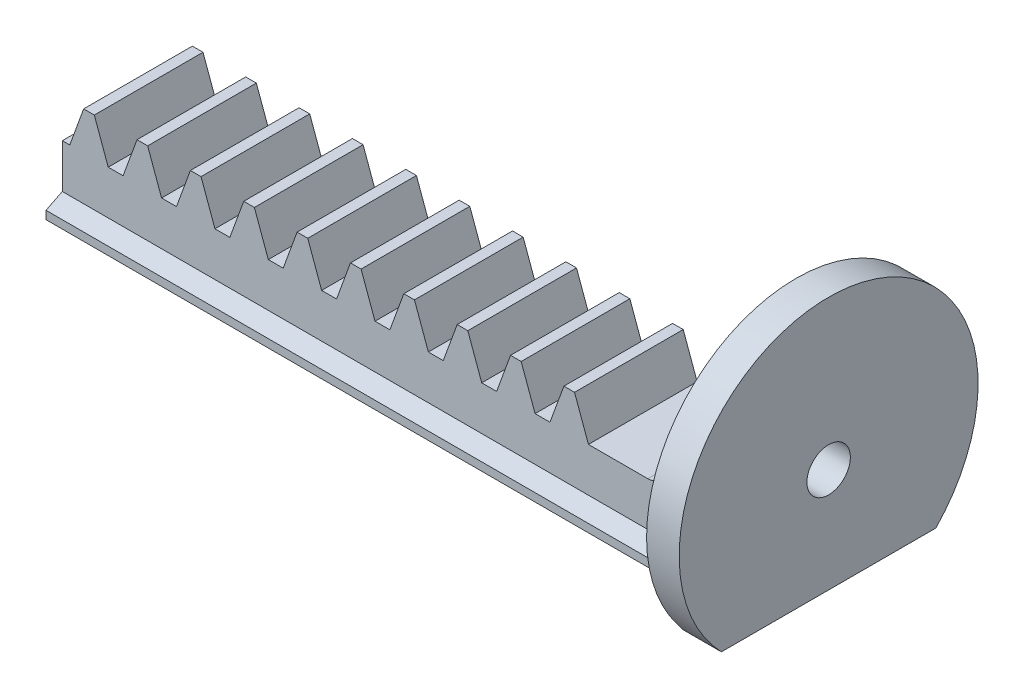
SolidWorks part; units mm, degrees
extrude "Blank" add sketch "BlankSke" against normal blind 6
sketch "BlankSke" plane through (0, 0, 0) normal (0, 0, 1) x (1, 0, 0)
  line L1 (0, 0) -> (40, 0)
  line L2 (0, 0) -> (0, 7.25)
  line L3 (0, 7.25) -> (40, 7.25)
  line L4 (40, 0) -> (40, 7.25)
  dimension "Length" = 40
  dimension "Blank_height" = 7.25
material "1060 合金"
ref_plane "Plane1" through (0, 0, 0) normal (0, 0, 1) x (1, 0, 0)
ref_plane "Plane2" through (0, 0, 0) normal (0, 1, 0) x (1, 0, 0)
ref_plane "Plane3" through (0, 0, 0) normal (1, 0, 0) x (0, 0, -1)
other "Configuration Table"
sketch "HoldingSke" plane through (0, 0, 0) normal (0, 1, 0) x (1, 0, 0)
  line L0 (0, 0) -> (0.1113, 0.7922)
  line L1 (-15, 0) -> (100, 0) construction
  line L2 (0, 0) -> (-2.1039, 2.3779)
  line L3 (0, 0) -> (-11.863, 4.5341)
  line L4 (0, 0) -> (8.4473, 1.7955)
  line L5 (0, 0) -> (-23.7986, -8.8762)
  line L6 (0, 0) -> (-10.5278, -7.1032)
  line L9 (-71.009, 38.7566) -> (-33.4213, 52.4374)
  line L10 (-76.2, 3.6279) -> (-70.2, 3.6279)
  line L11 (0, 0) -> (-6, 0)
  line L12 (-76.2, 101.6) -> (-76.155, 101.6)
  line L13 (24.9733, 27.94) -> (52.9518, 28.4284)
  line L14 (24.9733, 27.94) -> (24.9743, 27.94)
  line L15 (24.9733, 27.94) -> (100.4006, 29.5858)
  circle A0 centre (0, 0) radius 19.05
  circle A1 centre (0, 0) radius 3
  circle A2 centre (0, 0) radius 12.7
  dimension "MPH" = 6
  dimension "Diameter" = 38.1
  dimension "Num_teeth" = 12
  dimension "Pitch" = 0.8
  dimension "Show_teeth" = 998
  dimension "Thickness" = 12.7
  dimension "Ap" = 20
  dimension "Pitch_height" = 6
  dimension "Width" = 6
  dimension "Backlash" = 0.045
  dimension "Addendum_fac" = 1
  dimension "Dedendum_fac" = 1.25
  dimension "Clearance_fac" = 0.25
  dimension "Dedendum_add" = 0.001
  dimension "Length" = 40
  dimension "Module" = 1.25
sketch "TooCutSkeIll" plane through (0, 0, 0) normal (0, 0, 1) x (1, 0, 0)
  line L0 (-1.5597, 7.2171) -> (-0.6231, 4.6438)
  line L1 (-0.3285, 4.4375) -> (0.3285, 4.4375)
  line L2 (0.6231, 4.6438) -> (1.5597, 7.2171)
  line L3 (40, 7.25) -> (0, 7.25) construction
  line L4 (0, 0) -> (0, 64.897) construction
  line L5 (-13.208, 6) -> (12.954, 6) construction
  line L6 (0, 0) -> (40, 0) construction
  line L7 (1.1167, 6) -> (1.1167, 48.7463) construction
  line L8 (-1.1167, 6) -> (-1.1167, 48.7463) construction
  line L9 (1.6067, 7.25) -> (1.6067, 7.2754)
  line L10 (-1.6067, 7.25) -> (-1.6067, 7.2754)
  line L11 (-1.6067, 7.2754) -> (1.6067, 7.2754)
  arc A0 (0.3285, 4.4375) -> (0.6231, 4.6438) centre (0.3285, 4.751) ccw
  arc A1 (-0.6231, 4.6438) -> (-0.3285, 4.4375) centre (-0.3285, 4.751) ccw
  arc A2 (1.6067, 7.25) -> (1.5597, 7.2171) centre (1.6067, 7.2) ccw
  arc A3 (-1.5597, 7.2171) -> (-1.6067, 7.25) centre (-1.6067, 7.2) ccw
  dimension "Pitch_height" = 6
  dimension "Addendum_plus" = 1.2754
  dimension "Pressure_angle" = 20
  dimension "Gap_width" = 2.2335
  dimension "Dedendum" = 1.5625
extrude "ToothCutIll" [suppressed] cut sketch "TooCutSkeIll" against normal through all
sketch "TooCutSkeSim" plane through (0, 0, 0) normal (0, 0, 1) x (1, 0, 0)
  line L0 (0.548, 4.4375) -> (-0.548, 4.4375)
  line L1 (1.581, 7.2754) -> (0.548, 4.4375)
  line L2 (0, 17.4625) -> (0, 53.467) construction
  line L3 (1.581, 7.2754) -> (-1.581, 7.2754)
  line L6 (-1.581, 7.2754) -> (-0.548, 4.4375)
  line L9 (-1.1167, 6) -> (1.1167, 6) construction
  line L10 (0, 0) -> (40, 0) construction
  line L11 (1.1167, 6) -> (1.1167, 53.467) construction
  line L12 (-1.1167, 6) -> (-1.1167, 53.467) construction
  dimension "Pitch_height" = 6
  dimension "Addendum_plus" = 1.2754
  dimension "Pressure_angle" = 20
  dimension "Gap_width" = 2.2335
  dimension "Dedendum" = 1.5625
extrude "ToothCutSim" cut sketch "TooCutSkeSim" against normal through all
pattern_linear "TeethCuts" count 12 spacing 3.927 along (1, 0, 0) of "ToothCutIll", "ToothCutSim"
sketch "草图1" plane through (0, 0, 0) normal (0, 0, 1) x (1, 0, 0)
  line L0 (39.818, 4.4375) -> (41.3726, 4.4375)
  line L1 (41.3726, 4.4375) -> (41.3726, 5.3432)
  line L2 (41.3726, 5.3432) -> (39.818, 5.3432)
  line L3 (39.818, 5.3432) -> (39.818, 4.4375)
extrude "切除-拉伸1" cut sketch "草图1" against normal blind 10
sketch "草图2" plane through (0, 0, 0) normal (0, -1, 0) x (1, 0, 0)
  line L0 (40, 0) -> (50, 0)
  line L2 (50, 0) -> (50, -6)
  line L3 (50, -6) -> (40, -6)
  line L4 (40, -6) -> (40, 0)
  dimension "D1" = 10
extrude "凸台-拉伸1" add sketch "草图2" against normal up to surface (4.4375 mm away)
sketch "草图3" plane through (50, 0, 0) normal (1, 0, 0) x (0, 0, -1)
  line L0 (0, 4.4375) -> (0, 10.8887)
  line L1 (0, 10.8887) -> (6, 10.8887)
  line L2 (6, 10.8887) -> (6, 4.4375)
  line L3 (6, 4.4375) -> (6, 0) construction
  line L4 (0, 4.4375) -> (0, 0) construction
  line L5 (6, 0) -> (0, 0) construction
  line L6 (0, 4.4375) -> (0, 0)
  line L7 (6, 4.4375) -> (6, 0)
  line L8 (6, 0) -> (0, 0)
extrude "凸台-拉伸2" add sketch "草图3" along normal blind 2.4
sketch "草图4" plane through (50, 0, 0) normal (-1, 0, 0) x (0, 0, 1)
  line L0 (-6, 10.8887) -> (0, 4.4375) construction
  line L1 (0, 10.8887) -> (-6, 4.4375) construction
  line L2 (-6, 10.8887) -> (0, 10.8887) construction
  point P10 (-3, 7.6631)
  point P14 (-3, 7.6631)
hole_wizard "Ø3.0mm 暗销孔1" positions "草图4" profile "草图5" hole size "Ø3.0" standard "ISO" end condition through all
sketch "草图5" plane through (50, 7.6631, -3) normal (0, 1, 0) x (0, 0, 1)
  line L0 (0, 0) -> (0, 2.4)
  line L1 (0, 2.4) -> (1.6, 2.4)
  line L2 (1.6, 2.4) -> (1.6, 0)
  line L5 (1.6, 0) -> (0, 0)
  line L11 (0, -6.35) -> (0, 107.95) construction
  dimension "通孔孔直径" = 3.2
  dimension "通孔孔深度" = 2.4
sketch "草图6" plane through (0, 0, -6) normal (0, 0, -1) x (-1, 0, 0)
  line L0 (-38.7219, 4.4375) -> (-50, 4.4375) construction
  line L1 (0, 0) -> (-52.4, 0) construction
  line L2 (-52.4, 0) -> (-52.4, 10.8887) construction
  line L3 (-52.4, 10.8887) -> (-50, 10.8887) construction
  line L5 (-38.7219, 4.4375) -> (-43.5, 4.4375)
  line L6 (-38.7219, 0) -> (-52.4, 0)
  line L7 (-52.4, 0) -> (-52.4, 10.8887)
  line L8 (-52.4, 10.8887) -> (-50, 10.8887)
  line L10 (-38.7219, 4.4375) -> (-38.7219, 0)
  line L11 (-50, 10.8887) -> (-43.5, 4.4375)
  dimension "D1" = 6.5
extrude "凸台-拉伸3" add sketch "草图6" along normal blind 1
ref_plane "基准面1" through (0, 0, -3) normal (0, 0, -1) x (-1, 0, 0)
mirror "镜向1" about plane through (0, 0, -3) normal (0, 0, -1) of "凸台-拉伸3"
fillet "圆角1" radius 1 3 edges at (50, 4.4375, -3) (43.5, 4.4375, 0.5) (43.5, 4.4375, -6.5)
sketch "草图9" plane through (0, 0, -7) normal (0, 0, -1) x (-1, 0, 0)
  line L43 (-37.6982, 7.25) -> (-38.7219, 4.4375)
  line L44 (-38.7219, 4.4375) -> (-38.7219, 0)
  line L45 (-38.7219, 0) -> (0, 0)
  line L46 (0, 0) -> (0, 4.4375)
  line L47 (0, 4.4375) -> (-0.548, 4.4375)
  line L48 (-0.548, 4.4375) -> (-1.5717, 7.25)
  line L49 (-1.5717, 7.25) -> (-2.3553, 7.25)
  line L50 (-2.3553, 7.25) -> (-3.3789, 4.4375)
  line L51 (-3.3789, 4.4375) -> (-4.475, 4.4375)
  line L52 (-4.475, 4.4375) -> (-5.4987, 7.25)
  line L53 (-5.4987, 7.25) -> (-6.2823, 7.25)
  line L54 (-6.2823, 7.25) -> (-7.3059, 4.4375)
  line L55 (-7.3059, 4.4375) -> (-8.402, 4.4375)
  line L56 (-8.402, 4.4375) -> (-9.4257, 7.25)
  line L57 (-9.4257, 7.25) -> (-10.2093, 7.25)
  line L58 (-10.2093, 7.25) -> (-11.2329, 4.4375)
  line L59 (-11.2329, 4.4375) -> (-12.329, 4.4375)
  line L60 (-12.329, 4.4375) -> (-13.3527, 7.25)
  line L61 (-13.3527, 7.25) -> (-14.1363, 7.25)
  line L62 (-14.1363, 7.25) -> (-15.1599, 4.4375)
  line L63 (-15.1599, 4.4375) -> (-16.256, 4.4375)
  line L64 (-16.256, 4.4375) -> (-17.2797, 7.25)
  line L65 (-17.2797, 7.25) -> (-18.0632, 7.25)
  line L66 (-18.0632, 7.25) -> (-19.0869, 4.4375)
  line L67 (-19.0869, 4.4375) -> (-20.183, 4.4375)
  line L68 (-20.183, 4.4375) -> (-21.2067, 7.25)
  line L69 (-21.2067, 7.25) -> (-21.9902, 7.25)
  line L70 (-21.9902, 7.25) -> (-23.0139, 4.4375)
  line L71 (-23.0139, 4.4375) -> (-24.11, 4.4375)
  line L72 (-24.11, 4.4375) -> (-25.1337, 7.25)
  line L73 (-25.1337, 7.25) -> (-25.9172, 7.25)
  line L74 (-25.9172, 7.25) -> (-26.9409, 4.4375)
  line L75 (-26.9409, 4.4375) -> (-28.037, 4.4375)
  line L76 (-28.037, 4.4375) -> (-29.0606, 7.25)
  line L77 (-29.0606, 7.25) -> (-29.8442, 7.25)
  line L78 (-29.8442, 7.25) -> (-30.8679, 4.4375)
  line L79 (-30.8679, 4.4375) -> (-31.964, 4.4375)
  line L80 (-31.964, 4.4375) -> (-32.9876, 7.25)
  line L81 (-32.9876, 7.25) -> (-33.7712, 7.25)
  line L82 (-33.7712, 7.25) -> (-34.7949, 4.4375)
  line L83 (-34.7949, 4.4375) -> (-35.891, 4.4375)
  line L84 (-35.891, 4.4375) -> (-36.9146, 7.25)
  line L85 (-36.9146, 7.25) -> (-37.6982, 7.25)
  line L86 (-37.6982, 7.25) -> (-38.7219, 4.4375)
  line L87 (-38.7219, 4.4375) -> (-38.7219, 0)
  line L88 (-38.7219, 0) -> (0, 0)
  line L89 (0, 0) -> (0, 4.4375)
  line L90 (0, 4.4375) -> (-0.548, 4.4375)
  line L91 (-0.548, 4.4375) -> (-1.5717, 7.25)
  line L92 (-1.5717, 7.25) -> (-2.3553, 7.25)
  line L93 (-2.3553, 7.25) -> (-3.3789, 4.4375)
  line L94 (-3.3789, 4.4375) -> (-4.475, 4.4375)
  line L95 (-4.475, 4.4375) -> (-5.4987, 7.25)
  line L96 (-5.4987, 7.25) -> (-6.2823, 7.25)
  line L97 (-6.2823, 7.25) -> (-7.3059, 4.4375)
  line L98 (-7.3059, 4.4375) -> (-8.402, 4.4375)
  line L99 (-8.402, 4.4375) -> (-9.4257, 7.25)
  line L100 (-9.4257, 7.25) -> (-10.2093, 7.25)
  line L101 (-10.2093, 7.25) -> (-11.2329, 4.4375)
  line L102 (-11.2329, 4.4375) -> (-12.329, 4.4375)
  line L103 (-12.329, 4.4375) -> (-13.3527, 7.25)
  line L104 (-13.3527, 7.25) -> (-14.1363, 7.25)
  line L105 (-14.1363, 7.25) -> (-15.1599, 4.4375)
  line L106 (-15.1599, 4.4375) -> (-16.256, 4.4375)
  line L107 (-16.256, 4.4375) -> (-17.2797, 7.25)
  line L108 (-17.2797, 7.25) -> (-18.0632, 7.25)
  line L109 (-18.0632, 7.25) -> (-19.0869, 4.4375)
  line L110 (-19.0869, 4.4375) -> (-20.183, 4.4375)
  line L111 (-20.183, 4.4375) -> (-21.2067, 7.25)
  line L112 (-21.2067, 7.25) -> (-21.9902, 7.25)
  line L113 (-21.9902, 7.25) -> (-23.0139, 4.4375)
  line L114 (-23.0139, 4.4375) -> (-24.11, 4.4375)
  line L115 (-24.11, 4.4375) -> (-25.1337, 7.25)
  line L116 (-25.1337, 7.25) -> (-25.9172, 7.25)
  line L117 (-25.9172, 7.25) -> (-26.9409, 4.4375)
  line L118 (-26.9409, 4.4375) -> (-28.037, 4.4375)
  line L119 (-28.037, 4.4375) -> (-29.0606, 7.25)
  line L120 (-29.0606, 7.25) -> (-29.8442, 7.25)
  line L121 (-29.8442, 7.25) -> (-30.8679, 4.4375)
  line L122 (-30.8679, 4.4375) -> (-31.964, 4.4375)
  line L123 (-31.964, 4.4375) -> (-32.9876, 7.25)
  line L124 (-32.9876, 7.25) -> (-33.7712, 7.25)
  line L125 (-33.7712, 7.25) -> (-34.7949, 4.4375)
  line L126 (-34.7949, 4.4375) -> (-35.891, 4.4375)
  line L127 (-35.891, 4.4375) -> (-36.9146, 7.25)
  line L128 (-36.9146, 7.25) -> (-37.6982, 7.25)
  dimension "D1" = 0
extrude "凸台-拉伸4" add sketch "草图9" against normal up to surface (8 mm away) up to face at (45.5933, 5.0444, 1)
ref_plane "基准面2" through (52.4, 0, 0) normal (1, 0, 0) x (0, 0, -1)
sketch "草图10" plane through (52.4, 0, 0) normal (1, 0, 0) x (0, 0, -1)
  line L4 (7, 10.8887) -> (-1, 10.8887)
  line L5 (-1, 10.8887) -> (-1, 0)
  line L6 (-1, 0) -> (7, 0)
  line L7 (7, 0) -> (7, 10.8887)
  line L8 (7, 10.8887) -> (-1, 10.8887)
  line L9 (-1, 10.8887) -> (-1, 0)
  line L10 (-4.8916, 0) -> (10.8916, 0)
  line L11 (7, 0) -> (7, 10.8887)
  circle A0 centre (3, 7.6631) radius 1.6 construction
  circle A1 centre (3, 7.6631) radius 1.6 construction
  arc A2 (10.8916, 0) -> (-4.8916, 0) centre (3, 7.6631) ccw
  dimension "D2" = 22
  dimension "D1" = 0
extrude "凸台-拉伸5" add sketch "草图10" against normal up to surface (2.4 mm away) contours L10 A2 L9 L8 L11 region at (52.4, 11.1772, -3) up to face at (50, 7.6631, -1.4)
sketch3d "3D草图1"
  line L0 (50, 0, -7) -> (50, 0, -10.8916) construction
  line L1 (50, 0, -7) -> (50, 0, -10.8916)
  line L2 (50, 0, -10.8916) -> (50, 5.4444, -7)
  line L3 (50, 0, -7) -> (50, 10.8887, -7) construction
  line L4 (50, 5.4444, -7) -> (43.7667, 0, -7)
  line L5 (50, 0, -7) -> (0, 0, -7) construction
  line L6 (43.7667, 0, -7) -> (50, 0, -7)
  line L7 (50, 0, -7) -> (50, 5.4444, -7)
sketch "草图12" plane through (0, 0, -7) normal (0, 0, -1) x (-1, 0, 0)
  line L0 (-50, 5.4444) -> (-50, 0)
  line L1 (-50, 0) -> (-50, 10.8887) construction
  line L2 (-50, 0) -> (-43.748, 0)
  line L3 (-50, 0) -> (0, 0) construction
  line L4 (-43.748, 0) -> (-50, 5.4444)
sketch "草图13" plane through (50, 0, 0) normal (-1, 0, 0) x (0, 0, 1)
  point P0 (-10.8916, 0)
loft "放样1" add profiles "草图13", "草图12"
mirror "镜向8" about plane through (0, 0, -3) normal (0, 0, -1) of "放样1"
ref_plane "基准面3" through (0, 6, 0) normal (0, 1, 0) x (1, 0, 0)
sketch "草图14" plane through (0, 0, 0) normal (-1, 0, 0) x (0, 0, 1)
  line L2 (-7, 0) -> (-8.2, 0)
  line L3 (-7, 0) -> (-7, 1.2)
  line L4 (-7, 1.2) -> (-8.2, 1.2) construction
  line L5 (-8.2, 0) -> (-8.2, 1.2) construction
  line L6 (-8.2, 0.6) -> (-7, 1.2)
  line L7 (-8.2, 0.6) -> (-8.2, 0)
  dimension "D1" = 1.2
  dimension "D2" = 1.2
extrude "凸台-拉伸6" add sketch "草图14" against normal up to next
mirror "镜向9" about plane through (0, 0, -3) normal (0, 0, -1) of "凸台-拉伸6"
fillet "圆角3" radius 2 10 edges at (46.0204, 0.3, 2.2) (46.0204, 0.3, -8.2) (45.7454, 0.9, -7.6)
equation "' \"Module@HoldingSke\" = 6.35"
equation "' \"Num_teeth@HoldingSke\" = 12"
equation "' \"Ap@HoldingSke\" =  20"
equation "' \"Ap@HoldingSke\" = 20"
equation "' \"Width@HoldingSke\" = 0.25 * 25.4"
equation "' \"Show_teeth@HoldingSke\" = 500"
equation "' \"Backlash@HoldingSke\" = 0.009 * 25.4"
equation "' \"Addendum_fac@HoldingSke\" = 1.0"
equation "' \"Dedendum_fac@HoldingSke\" = 1.25"
equation "' \"Dedendum_add@HoldingSke\" = 0.00005 * 25.4"
equation "' \"Clearance_fac@HoldingSke\" = 0.25"
equation "' \"Pitch_height@HoldingSke\" = 1 * 25.4"
equation "' \"Length@HoldingSke\" = 4.71 * 25.4"
equation "\"Pitch@HoldingSke\" = 1 / \"Module@HoldingSke\""
equation "\"MPH@HoldingSke\" = \"Dedendum_fac@HoldingSke\" / \"Pitch@HoldingSke\" + 2 * \"Dedendum_add@HoldingSke\" + 0.002 * 25.4"
equation "\"MPH@HoldingSke\" = ((sgn( \"MPH@HoldingSke\" - \"Pitch_height@HoldingSke\")+1)*( \"MPH@HoldingSke\" - \"Pitch_height@HoldingSke\"))/2 + \"Pitch_height@HoldingSke\""
equation "\"Blank_height@BlankSke\" = \"Pitch_height@HoldingSke\" + \"Addendum_fac@HoldingSke\"  / \"Pitch@HoldingSke\" "
equation "\"Length@BlankSke\" =  \"Length@HoldingSke\""
equation "\"Face_width@Blank\" = \"Width@HoldingSke\""
equation "\"Pressure_angle@TooCutSkeIll\" = \"Ap@HoldingSke\""
equation "\"Addendum_plus@TooCutSkeIll\" =  \"Addendum_fac@HoldingSke\"  / \"Pitch@HoldingSke\" + 0.001 *25.4"
equation "\"Dedendum@TooCutSkeIll\" = \"Dedendum_fac@HoldingSke\"  / \"Pitch@HoldingSke\""
equation "\"Pitch_height@TooCutSkeIll\" =  \"MPH@HoldingSke\""
equation "\"Gap_width@TooCutSkeIll\" = 3.14159265 / 2 / \"Pitch@HoldingSke\" + 6 * \"Backlash@HoldingSke\""
equation "\"Pressure_angle@TooCutSkeSim\" = \"Ap@HoldingSke\""
equation "\"Addendum_plus@TooCutSkeSim\" =  \"Addendum_fac@HoldingSke\"  / \"Pitch@HoldingSke\" + 0.001 * 25.4"
equation "\"Dedendum@TooCutSkeSim\" = \"Dedendum_fac@HoldingSke\"  / \"Pitch@HoldingSke\""
equation "\"Pitch_height@TooCutSkeSim\" =  \"MPH@HoldingSke\""
equation "\"Gap_width@TooCutSkeSim\" = 3.14159265 / 2 / \"Pitch@HoldingSke\" + 6 * \"Backlash@HoldingSke\""
equation "\"Root_fillet@TooCutSkeIll\" = \"Clearance_fac@HoldingSke\" / \"Pitch@HoldingSke\" + \"Dedendum_add@HoldingSke\""
equation "\"Break_rad@TooCutSkeIll\" = 0.02 / \"Pitch@HoldingSke\" * 2"
equation "\"Linear_pitch@TeethCuts\" = 3.14159265 / \"Pitch@HoldingSke\""
equation "\"Num_teeth@HoldingSke\" = int( ( \"Length@HoldingSke\" + 0 ) / (3.14159265 / \"Pitch@HoldingSke\")) + 0.9999  + 1"
equation " \"Num_teeth@TeethCuts\" = int( \"Show_teeth@HoldingSke\" ) + 1"
equation " \"Num_teeth@TeethCuts\" = ((sgn( \"Num_teeth@TeethCuts\" - \"Num_teeth@HoldingSke\" )-1)*( \"Num_teeth@TeethCuts\" - \"Num_teeth@HoldingSke\" ))/-2+ \"Num_teeth@HoldingSke\""
equation " \"Num_teeth@TeethCuts\" = ((sgn( \"Num_teeth@TeethCuts\" - 2.0)+1)*( \"Num_teeth@TeethCuts\" - 2.0))/2 +2.0"
